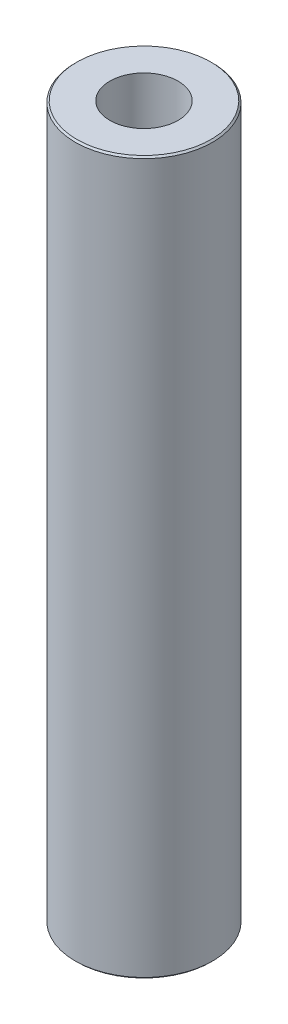
SolidWorks part; units mm, degrees
ref_plane "Front Plane" through (0, 0, 0) normal (0, 0, 1) x (1, 0, 0)
ref_plane "Top Plane" through (0, 0, 0) normal (0, 1, 0) x (1, 0, 0)
ref_plane "Right Plane" through (0, 0, 0) normal (1, 0, 0) x (0, 0, -1)
sketch "Sketch1" plane through (0, 0, 0) normal (0, 1, 0) x (1, 0, 0)
  circle A0 centre (0, 0) radius 55
  dimension "SHAFT_OD" = 110
extrude "Boss-Extrude1" add sketch "Sketch1" along normal blind 570.3629
sketch "Sketch2" plane through (0, 0, 0) normal (0, 1, 0) x (1, 0, 0)
  circle A0 centre (0, 0) radius 27.3058
  dimension "BORE_D" = 54.6117
extrude "Cut-Extrude1" cut sketch "Sketch2" along normal through all
chamfer "Chamfer1" distance 1.3009 angle 45 2 edges at (0, 570.3629, 55) (0, 0, 55)
